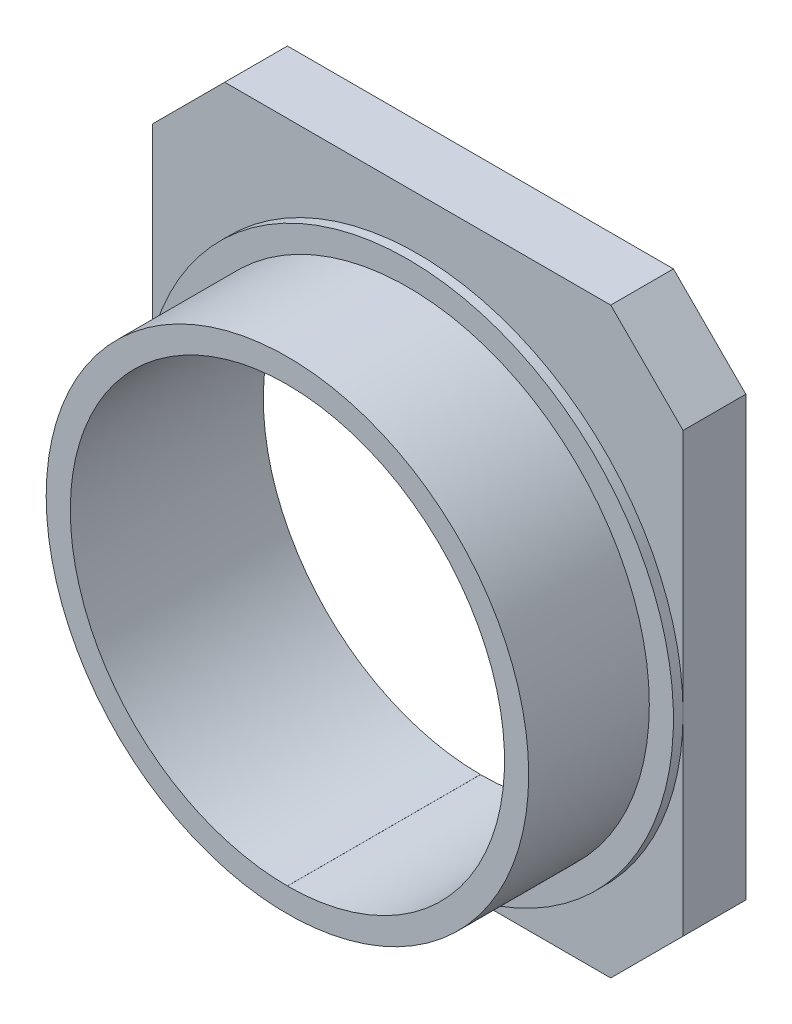
SolidWorks part; units mm, degrees
ref_plane "前视基准面" through (0, 0, 0) normal (0, 0, 1) x (1, 0, 0)
ref_plane "上视基准面" through (0, 0, 0) normal (0, 1, 0) x (1, 0, 0)
ref_plane "右视基准面" through (0, 0, 0) normal (1, 0, 0) x (0, 0, -1)
sketch "Sketch1" plane through (0, 0, 0) normal (0, 0, 1) x (1, 0, 0)
  line L14 (-101.8275, -139.2546) -> (-109.8275, -139.2546)
  line L15 (-109.8275, -139.2546) -> (-112.8275, -142.2546)
  line L16 (-112.8275, -142.2546) -> (-112.8275, -160.4104)
  line L17 (-112.8275, -160.4104) -> (-109.8275, -163.4104)
  line L18 (-109.8275, -163.4104) -> (-101.8275, -163.4104)
  line L19 (-101.8275, -161.4104) -> (-101.8275, -161.4068)
  line L21 (-90.8275, -142.2546) -> (-93.8275, -139.2546)
  line L22 (-93.8275, -139.2546) -> (-101.8275, -139.2546)
  line L23 (-101.8275, -143.4071) -> (-101.8275, -143.4104)
  line L25 (-101.8275, -163.4104) -> (-93.8275, -163.4104)
  line L26 (-93.8275, -163.4104) -> (-90.8275, -160.4104)
  line L27 (-90.8275, -160.4104) -> (-90.8275, -142.2546)
  arc A1 (-101.8275, -161.4104) -> (-101.8275, -143.4104) centre (-101.8275, -152.4104) ccw
  spline S1 degree 3 poles (-101.8275, -161.4068) (-102.4222, -161.4068) (-103.0069, -161.3485) (-103.8696, -161.177) (-104.1548, -161.1057) (-104.7203, -160.9344) (-105.0013, -160.8338) (-105.8188, -160.4949) (-106.3358, -160.2185) (-107.3142, -159.5652) (-107.7774, -159.185) (-108.6077, -158.3545) (-108.9803, -157.9013) (-109.4737, -157.1633) (-109.6269, -156.9076) (-109.9045, -156.3879) (-110.1553, -155.8572) (-110.3533, -155.3048) (-110.5245, -154.7414) (-110.597, -154.4526) (-110.7702, -153.5812) (-110.8273, -152.9972) (-110.8276, -152.1167) (-110.8134, -151.8224) (-110.7555, -151.2323) (-110.7118, -150.9384) (-110.5394, -150.0726) (-110.3694, -149.5116) (-110.0313, -148.6943) (-109.9039, -148.4246) (-109.6251, -147.9031) (-109.4738, -147.6509) (-108.985, -146.9194) (-108.613, -146.4648) (-107.773, -145.6245) (-107.3174, -145.2513) (-106.5862, -144.7625) (-106.3343, -144.6112) (-105.8137, -144.3326) (-105.5439, -144.2049) (-104.7257, -143.8661) (-104.1646, -143.696) (-103.0114, -143.466) (-102.4149, -143.4071) (-101.8275, -143.4071) knots 0 0 0 0 0.0625 0.0625 0.09375 0.09375 0.125 0.125 0.1875 0.1875 0.25 0.25 0.3125 0.3125 0.34375 0.34375 0.375 0.40625 0.40625 0.4375 0.4375 0.5 0.5 0.53125 0.53125 0.5625 0.5625 0.625 0.625 0.65625 0.65625 0.6875 0.6875 0.75 0.75 0.8125 0.8125 0.84375 0.84375 0.875 0.875 0.9375 0.9375 1 1 1 1
extrude "Boss-Extrude1" add sketch "Sketch1" along normal blind 2.6
sketch "Sketch2" plane through (0, 0, 3) normal (0, 0, -1) x (-1, 0, 0)
  line L2 (101.8275, -161.4104) -> (101.8275, -161.4068)
  line L3 (101.8275, -143.4071) -> (101.8275, -143.4104)
  line L4 (101.8275, -161.4104) -> (101.8275, -161.4068)
  line L5 (101.8275, -143.4071) -> (101.8275, -143.4104)
  circle A3 centre (101.8275, -152.4104) radius 11
  arc A5 (101.8275, -143.4104) -> (101.8275, -161.4104) centre (101.8275, -152.4104) ccw
  arc A6 (101.8275, -143.4104) -> (101.8275, -161.4104) centre (101.8275, -152.4104) ccw
  spline S2 degree 3 poles (-738.2887, 3747.0312) (-103.1659, 362.6876) (46.7445, -172.5311) (103.8696, -161.177) (104.1548, -161.1057) (104.7203, -160.9344) (105.0013, -160.8338) (105.8188, -160.4949) (106.3358, -160.2185) (107.3142, -159.5652) (107.7774, -159.185) (108.6077, -158.3545) (108.9803, -157.9013) (109.4737, -157.1633) (109.6269, -156.9076) (109.9045, -156.3879) (110.1553, -155.8572) (110.3533, -155.3048) (110.5245, -154.7414) (110.597, -154.4526) (110.7702, -153.5812) (110.8273, -152.9972) (110.8276, -152.1167) (110.8134, -151.8224) (110.7555, -151.2323) (110.7118, -150.9384) (110.5394, -150.0726) (110.3694, -149.5116) (110.0313, -148.6943) (109.9039, -148.4246) (109.6251, -147.9031) (109.4738, -147.6509) (108.985, -146.9194) (108.613, -146.4648) (107.773, -145.6245) (107.3174, -145.2513) (106.5862, -144.7625) (106.3343, -144.6112) (105.8137, -144.3326) (105.5439, -144.2049) (104.7257, -143.8661) (104.1646, -143.696) (73.4243, -137.5645) (-11.2802, -285.2221) (4010.747, -973.5262) knots -6.113597 -6.113597 -6.113597 -6.113597 0.0625 0.0625 0.09375 0.09375 0.125 0.125 0.1875 0.1875 0.25 0.25 0.3125 0.3125 0.34375 0.34375 0.375 0.40625 0.40625 0.4375 0.4375 0.5 0.5 0.53125 0.53125 0.5625 0.5625 0.625 0.625 0.65625 0.65625 0.6875 0.6875 0.75 0.75 0.8125 0.8125 0.84375 0.84375 0.875 0.875 0.9375 0.9375 4.207105 4.207105 4.207105 4.207105 only from (101.8275, -161.4068) to (101.8275, -143.4071)
  spline S3 degree 3 poles (101.8275, -161.4068) (102.4222, -161.4068) (103.0069, -161.3485) (103.8696, -161.177) (104.1548, -161.1057) (104.7203, -160.9344) (105.0013, -160.8338) (105.8188, -160.4949) (106.3358, -160.2185) (107.3142, -159.5652) (107.7774, -159.185) (108.6077, -158.3545) (108.9803, -157.9013) (109.4737, -157.1633) (109.6269, -156.9076) (109.9045, -156.3879) (110.1553, -155.8572) (110.3533, -155.3048) (110.5245, -154.7414) (110.597, -154.4526) (110.7702, -153.5812) (110.8273, -152.9972) (110.8276, -152.1167) (110.8134, -151.8224) (110.7555, -151.2323) (110.7118, -150.9384) (110.5394, -150.0726) (110.3694, -149.5116) (110.0313, -148.6943) (109.9039, -148.4246) (109.6251, -147.9031) (109.4738, -147.6509) (108.985, -146.9194) (108.613, -146.4648) (107.773, -145.6245) (107.3174, -145.2513) (106.5862, -144.7625) (106.3343, -144.6112) (105.8137, -144.3326) (105.5439, -144.2049) (104.7257, -143.8661) (104.1646, -143.696) (103.0114, -143.466) (102.4149, -143.4071) (101.8275, -143.4071) knots 0 0 0 0 0.0625 0.0625 0.09375 0.09375 0.125 0.125 0.1875 0.1875 0.25 0.25 0.3125 0.3125 0.34375 0.34375 0.375 0.40625 0.40625 0.4375 0.4375 0.5 0.5 0.53125 0.53125 0.5625 0.5625 0.625 0.625 0.65625 0.65625 0.6875 0.6875 0.75 0.75 0.8125 0.8125 0.84375 0.84375 0.875 0.875 0.9375 0.9375 1 1 1 1
  dimension "D1" = 0
extrude "Boss-Extrude2" add sketch "Sketch2" along normal up to surface (0.4 mm away) up to face at (-101.8275, -151.3325, 2.6)
sketch "Sketch3" plane through (0, 0, 3) normal (0, 0, 1) x (1, 0, 0)
  line L2 (-101.8275, -161.4068) -> (-101.8275, -161.4104)
  line L3 (-101.8275, -143.4104) -> (-101.8275, -143.4071)
  line L4 (-101.8275, -161.4068) -> (-101.8275, -161.4104)
  line L5 (-101.8275, -143.4104) -> (-101.8275, -143.4071)
  arc A1 (-101.8275, -161.4104) -> (-101.8275, -143.4104) centre (-101.8275, -152.4104) ccw
  arc A2 (-101.8275, -161.4104) -> (-101.8275, -143.4104) centre (-101.8275, -152.4104) ccw
  circle A3 centre (-101.8275, -152.4104) radius 10
  spline S1 degree 3 poles (-5983.3072, -1300.3692) (36.4225, -330.2307) (-69.1433, -136.7106) (-104.1646, -143.696) (-104.7257, -143.8661) (-105.5439, -144.2049) (-105.8137, -144.3326) (-106.3343, -144.6112) (-106.5862, -144.7625) (-107.3174, -145.2513) (-107.773, -145.6245) (-108.613, -146.4648) (-108.985, -146.9194) (-109.4738, -147.6509) (-109.6251, -147.9031) (-109.9039, -148.4246) (-110.0313, -148.6943) (-110.3694, -149.5116) (-110.5394, -150.0726) (-110.7118, -150.9384) (-110.7555, -151.2323) (-110.8134, -151.8224) (-110.8276, -152.1167) (-110.8273, -152.9972) (-110.7702, -153.5812) (-110.597, -154.4526) (-110.5245, -154.7414) (-110.3533, -155.3048) (-110.1553, -155.8572) (-109.9045, -156.3879) (-109.6269, -156.9076) (-109.4737, -157.1633) (-108.9803, -157.9013) (-108.6077, -158.3545) (-107.7774, -159.185) (-107.3142, -159.5652) (-106.3358, -160.2185) (-105.8188, -160.4949) (-105.0013, -160.8338) (-104.7203, -160.9344) (-104.1548, -161.1057) (-103.8696, -161.177) (-37.1593, -174.4362) (156.3754, 558.7518) (1102.8943, 5713.3969) knots -3.671149 -3.671149 -3.671149 -3.671149 0.0625 0.0625 0.125 0.125 0.15625 0.15625 0.1875 0.1875 0.25 0.25 0.3125 0.3125 0.34375 0.34375 0.375 0.375 0.4375 0.4375 0.46875 0.46875 0.5 0.5 0.5625 0.5625 0.59375 0.59375 0.625 0.65625 0.65625 0.6875 0.6875 0.75 0.75 0.8125 0.8125 0.875 0.875 0.90625 0.90625 0.9375 0.9375 8.155149 8.155149 8.155149 8.155149 only from (-101.8275, -143.4071) to (-101.8275, -161.4068)
  spline S2 degree 3 poles (-101.8275, -143.4071) (-102.4149, -143.4071) (-103.0114, -143.466) (-104.1646, -143.696) (-104.7257, -143.8661) (-105.5439, -144.2049) (-105.8137, -144.3326) (-106.3343, -144.6112) (-106.5862, -144.7625) (-107.3174, -145.2513) (-107.773, -145.6245) (-108.613, -146.4648) (-108.985, -146.9194) (-109.4738, -147.6509) (-109.6251, -147.9031) (-109.9039, -148.4246) (-110.0313, -148.6943) (-110.3694, -149.5116) (-110.5394, -150.0726) (-110.7118, -150.9384) (-110.7555, -151.2323) (-110.8134, -151.8224) (-110.8276, -152.1167) (-110.8273, -152.9972) (-110.7702, -153.5812) (-110.597, -154.4526) (-110.5245, -154.7414) (-110.3533, -155.3048) (-110.1553, -155.8572) (-109.9045, -156.3879) (-109.6269, -156.9076) (-109.4737, -157.1633) (-108.9803, -157.9013) (-108.6077, -158.3545) (-107.7774, -159.185) (-107.3142, -159.5652) (-106.3358, -160.2185) (-105.8188, -160.4949) (-105.0013, -160.8338) (-104.7203, -160.9344) (-104.1548, -161.1057) (-103.8696, -161.177) (-103.0069, -161.3485) (-102.4222, -161.4068) (-101.8275, -161.4068) knots 0 0 0 0 0.0625 0.0625 0.125 0.125 0.15625 0.15625 0.1875 0.1875 0.25 0.25 0.3125 0.3125 0.34375 0.34375 0.375 0.375 0.4375 0.4375 0.46875 0.46875 0.5 0.5 0.5625 0.5625 0.59375 0.59375 0.625 0.65625 0.65625 0.6875 0.6875 0.75 0.75 0.8125 0.8125 0.875 0.875 0.90625 0.90625 0.9375 0.9375 1 1 1 1
  dimension "D1" = 0
extrude "Boss-Extrude3" add sketch "Sketch3" along normal up to surface (5 mm away)
